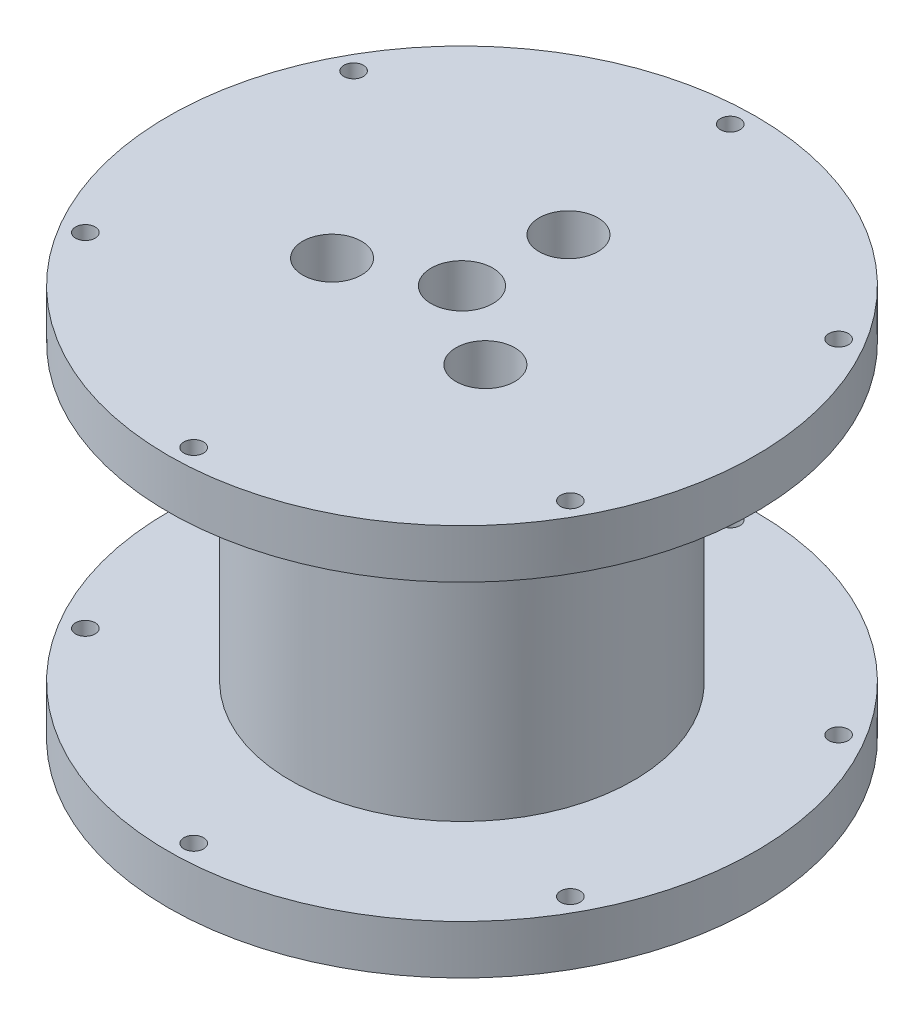
SolidWorks part; units mm, degrees
ref_plane "Front Plane" through (0, 0, 0) normal (0, 0, 1) x (1, 0, 0)
ref_plane "Top Plane" through (0, 0, 0) normal (0, 1, 0) x (1, 0, 0)
ref_plane "Right Plane" through (0, 0, 0) normal (1, 0, 0) x (0, 0, -1)
sketch "Sketch1" plane through (0, 0, 0) normal (0, 1, 0) x (1, 0, 0)
  circle A0 centre (0, 0) radius 30
extrude "Boss-Extrude1" add sketch "Sketch1" along normal blind 40
sketch "Sketch2" plane through (0, 0, 0) normal (0, -1, 0) x (1, 0, 0)
  circle A1 centre (0, 0) radius 17.5
extrude "Cut-Extrude1" cut sketch "Sketch2" against normal blind 30 from offset 5 flip side to cut offset against normal yes
sketch "Sketch3" plane through (0, 0, 0) normal (0, -1, 0) x (1, 0, 0)
  circle A0 centre (0, 0) radius 3.15
  dimension "D1" = 6.3
extrude "Cut-Extrude2" cut sketch "Sketch3" against normal through all
sketch "Sketch4" plane through (0, 0, 0) normal (0, -1, 0) x (1, 0, 0)
  line L1 (-16.3289, -11.5485) -> (18.1657, -8.367)
  line L2 (18.1657, -8.367) -> (-1.8368, 19.9155)
  line L3 (-1.8368, 19.9155) -> (-16.3289, -11.5485)
  circle A0 centre (0, 0) radius 10 construction
  circle A1 centre (8.1644, 5.7742) radius 3
  circle A2 centre (0.9184, -9.9577) radius 3
  circle A3 centre (-9.0829, 4.1835) radius 3
  point P1 (8.1644, 5.7742)
  point P7 (0.9184, -9.9577)
  point P8 (-9.0829, 4.1835)
  dimension "D1" = 6
  dimension "D2" = 6
  dimension "D3" = 6
  dimension "D4" = 20
extrude "Cut-Extrude3" cut sketch "Sketch4" against normal through all contours L1 A2 | L1 A2 | L2 A1 | L2 A1 | L3 A3 | L3 A3 region at (0.8015, 0, -8.6899) region at (1.0353, 0, -11.2256) region at (-10.2393, 0, 4.7162) region at (-7.9264, 0, 3.6508) region at (7.1249, 0, 5.039) region at (9.204, 0, 6.5094)
sketch "Sketch5" plane through (0, 5, 0) normal (0, 1, 0) x (1, 0, 0)
  circle A0 centre (-15.3397, 8.4227) radius 2
  circle A1 centre (0, 0) radius 17.5 construction
extrude "Cut-Extrude4" cut sketch "Sketch5" against normal up to next from offset 3
sketch "Sketch6" plane through (0, 0, 0) normal (0, -1, 0) x (1, 0, 0)
  line L1 (-6.0622, 0) -> (-3.0311, -5.25)
  line L2 (-3.0311, -5.25) -> (3.0311, -5.25)
  line L3 (3.0311, -5.25) -> (6.0622, 0)
  line L4 (6.0622, 0) -> (3.0311, 5.25)
  line L5 (3.0311, 5.25) -> (-3.0311, 5.25)
  line L6 (-3.0311, 5.25) -> (-6.0622, 0)
  circle A0 centre (0, 0) radius 5.25 construction
  dimension "D1" = 10.5
extrude "Cut-Extrude5" cut sketch "Sketch6" against normal blind 7.5
fillet "Fillet1" radius 2 1 edges at (-13.5866, 8, -7.4601)
sketch "Sketch7" plane through (0, 0, 0) normal (0, -1, 0) x (-1, 0, 0)
  line L0 (15.3397, 8.4227) -> (0, 0) construction
  line L1 (0, 0) -> (-26.2967, -14.439) construction
  line L3 (-24.5436, -13.4764) -> (-0.6009, -27.9936)
  line L4 (-0.6009, -27.9936) -> (23.9427, -14.5172)
  line L5 (23.9427, -14.5172) -> (24.5436, 13.4764)
  line L6 (24.5436, 13.4764) -> (0.6009, 27.9936)
  line L7 (0.6009, 27.9936) -> (-23.9427, 14.5172)
  line L8 (-23.9427, 14.5172) -> (-24.5436, -13.4764)
  circle A0 centre (0, 0) radius 30 construction
  circle A1 centre (-24.5436, -13.4764) radius 1
  circle A2 centre (0, 0) radius 24.2487 construction
  circle A3 centre (-0.6009, -27.9936) radius 1
  circle A4 centre (23.9427, -14.5172) radius 1
  circle A5 centre (24.5436, 13.4764) radius 1
  circle A6 centre (0.6009, 27.9936) radius 1
  circle A7 centre (-23.9427, 14.5172) radius 1
  dimension "D1" = 2
  dimension "D2" = 2
  dimension "D3" = 2
  dimension "D4" = 2
  dimension "D5" = 2
  dimension "D6" = 2
  dimension "D7" = 2
extrude "Cut-Extrude6" cut sketch "Sketch7" against normal through all both and the other way through all contours L3 A1 L8 | L8 A1 L3 | L4 A3 L3 | L3 A3 L4 | L5 A4 L4 | L4 A4 L5 | L6 A5 L5 | L5 A5 L6 | L6 A6 L7 | L7 A6 L6 | L7 A7 L8 | L8 A7 L7 region at (24.0603, 0, 13.211) region at (24.7852, 0, 13.6091) region at (0.5891, 0, 27.4423) region at (0.6068, 0, 28.2692) region at (24.1784, 0, -14.6601) region at (23.4712, 0, -14.2313) region at (-23.4712, 0, 14.2313) region at (-24.1784, 0, 14.6601) region at (-0.6068, 0, -28.2692) region at (-0.5891, 0, -27.4423) region at (-24.0603, 0, -13.211) region at (-24.7852, 0, -13.6091)
